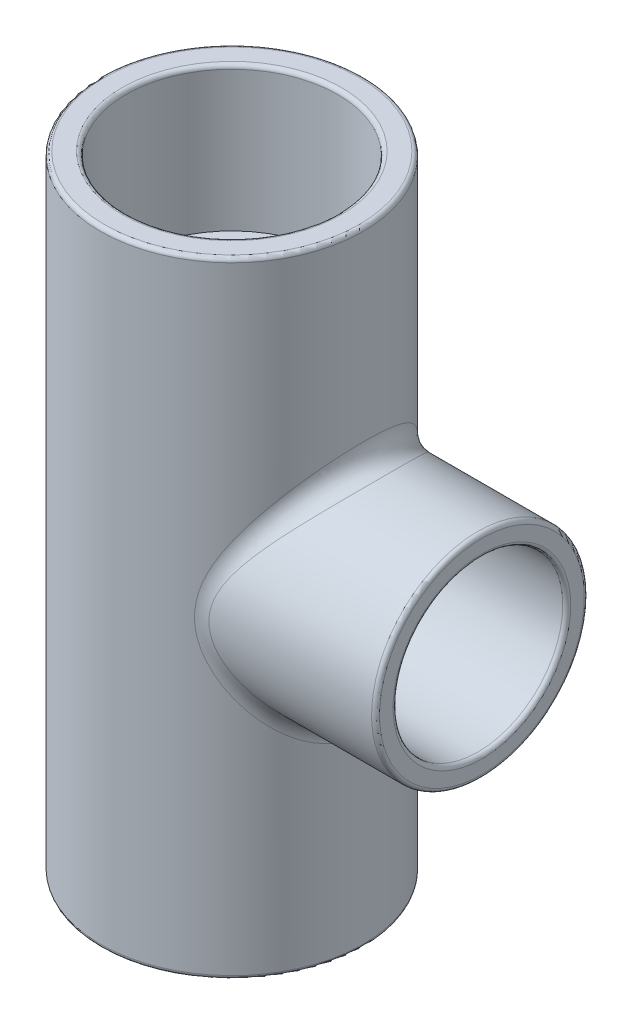
SolidWorks part; units mm, degrees
ref_plane "Front Plane" through (0, 0, 0) normal (0, 0, 1) x (1, 0, 0)
ref_plane "Top Plane" through (0, 0, 0) normal (0, 1, 0) x (1, 0, 0)
ref_plane "Right Plane" through (0, 0, 0) normal (1, 0, 0) x (0, 0, -1)
sketch "Sketch1" plane through (0, 0, 0) normal (0, 1, 0) x (1, 0, 0)
  circle A0 centre (0, 0) radius 656.5
  circle A1 centre (0, 0) radius 412
  dimension "D1" = 824
  dimension "D2" = 1313
extrude "Boss-Extrude1" add sketch "Sketch1" along normal blind 3125
sketch "Sketch2" plane through (0, 0, 0) normal (0, -1, 0) x (1, 0, 0)
  circle A0 centre (0, 0) radius 529
  dimension "D1" = 1058
extrude "Cut-Extrude1" cut sketch "Sketch2" against normal blind 720
sketch "Sketch3" plane through (0, 0, 0) normal (1, 0, 0) x (0, 0, -1)
  line L0 (0, 0) -> (0, 3125) construction
  line L1 (412, 3125) -> (-412, 3125) construction
  circle A0 centre (0, 1562.5) radius 531.5
  circle A1 centre (0, 1562.5) radius 311
  dimension "D1" = 1063
  dimension "D2" = 622
extrude "Boss-Extrude2" add sketch "Sketch3" along normal blind 1250
sketch "Sketch4" plane through (1250, 0, 0) normal (1, 0, 0) x (0, 0, -1)
  circle A0 centre (0, 1562.5) radius 424
  dimension "D1" = 848
extrude "Cut-Extrude2" cut sketch "Sketch4" against normal blind 690
sketch "Sketch6" plane through (0, 3125, 0) normal (0, 1, 0) x (1, 0, 0)
  line L0 (0, 412) -> (0, -412) construction
  circle A0 centre (0, 0) radius 529
  dimension "D1" = 1058
extrude "Cut-Extrude3" cut sketch "Sketch6" against normal blind 720
sketch "Sketch7" plane through (0, 3125, 0) normal (0, 1, 0) x (1, 0, 0)
  circle A0 centre (0, 0) radius 412
extrude "Cut-Extrude4" cut sketch "Sketch7" against normal through all
sketch "Sketch9" plane through (560, 0, 0) normal (1, 0, 0) x (0, 0, -1)
  line L0 (0, 0) -> (0, 3125) construction
  line L1 (656.5, 3125) -> (-656.5, 3125) construction
sketch "Sketch10" plane through (1250, 0, 0) normal (1, 0, 0) x (0, 0, -1)
  line L0 (0, 0) -> (0, 3125) construction
  circle A0 centre (0, 1562.5) radius 311
  dimension "D1" = 622
extrude "Cut-Extrude6" cut sketch "Sketch10" against normal blind 1250
fillet "Fillet2" radius 100 1 edges at (394.8782, 1648.6906, -524.4649)
fillet "Fillet3" radius 20 2 edges at (0, 0, 656.5) (0, 0, -529)
fillet "Fillet4" radius 20 2 edges at (0, 3125, 656.5) (0, 3125, 529)
fillet "Fillet5" radius 20 2 edges at (1250, 1562.5, -531.5) (1250, 1562.5, -424)
